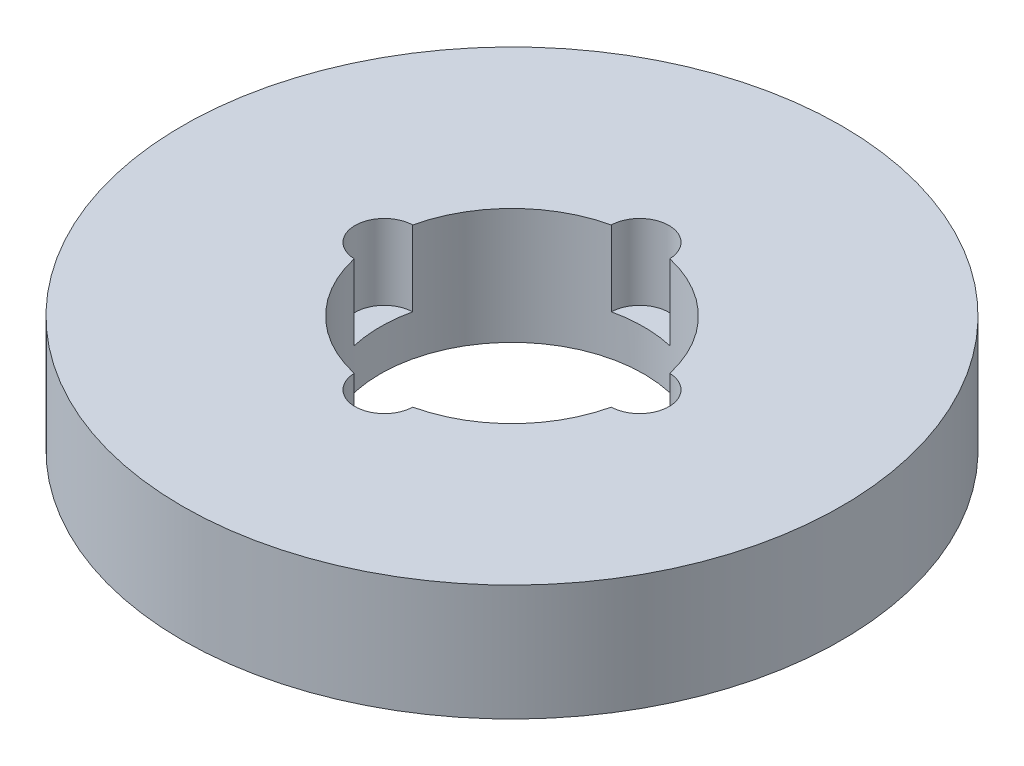
SolidWorks part; units mm, degrees
ref_plane "Front Plane" through (0, 0, 0) normal (0, 0, 1) x (1, 0, 0)
ref_plane "Top Plane" through (0, 0, 0) normal (0, 1, 0) x (1, 0, 0)
ref_plane "Right Plane" through (0, 0, 0) normal (1, 0, 0) x (0, 0, -1)
sketch "Sketch1" plane through (0, 0, 0) normal (0, 1, 0) x (1, 0, 0)
  circle A0 centre (0, 0) radius 62.5
  dimension "FLANGE_OD" = 125
extrude "Boss-Extrude1" add sketch "Sketch1" along normal blind 22
sketch "Sketch2" plane through (0, 0, 0) normal (0, 1, 0) x (1, 0, 0)
  circle A0 centre (0, 0) radius 25
  dimension "BORE_D" = 50
extrude "Cut-Extrude1" cut sketch "Sketch2" along normal through all
sketch "Sketch3" plane through (0, 22, 0) normal (0, 1, 0) x (1, 0, 0)
  circle A0 centre (0, 0) radius 24.2119 construction
  circle A1 centre (-24.2119, 0) radius 5.5503
  dimension "BOLT_D" = 11.1006
  dimension "BOLT_PCD" = 48.4237
extrude "Cut-Extrude2" cut sketch "Sketch3" against normal blind 14.2746
pattern_circular "CirPattern1" count 4 over 360 about axis through (0, 0, 0) along (0, 1, 0) of "Cut-Extrude2"
